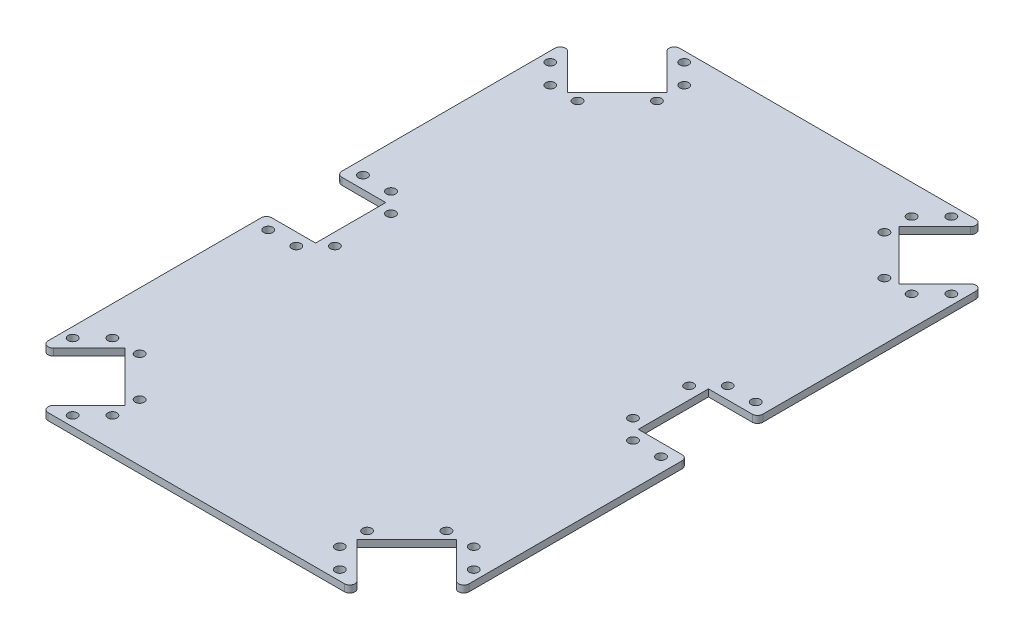
SolidWorks part; units mm, degrees
ref_plane "Front Plane" through (0, 0, 0) normal (0, 0, 1) x (1, 0, 0)
ref_plane "Top Plane" through (0, 0, 0) normal (0, 1, 0) x (1, 0, 0)
ref_plane "Right Plane" through (0, 0, 0) normal (1, 0, 0) x (0, 0, -1)
sketch "Sketch2" plane through (0, 0, 0) normal (0, 1, 0) x (1, 0, 0)
  line L0 (-60, 0) -> (60, 0) construction
  line L1 (-60, 90) -> (60, 90)
  line L2 (-60, 90) -> (-60, -90)
  line L3 (-60, -90) -> (60, -90)
  line L4 (60, 90) -> (60, -90)
  line L5 (60, 90) -> (0, 30) construction
  line L7 (0, 90) -> (0, -90) construction
  line L8 (32.4228, 73.7365) -> (28.5337, 77.6256) construction
  line L9 (28.5337, 77.6256) -> (32.4228, 81.5147) construction
  line L10 (32.4228, 81.5147) -> (38.0797, 87.1716) construction
  line L11 (38.0797, 87.1716) -> (40.9081, 90) construction
  circle A5 centre (32.4228, 73.7365) radius 1.3
  circle A6 centre (32.4228, 81.5147) radius 1.3
  circle A7 centre (38.0797, 87.1716) radius 1.3
  circle A8 centre (56, 13.5) radius 1.3
  circle A9 centre (48, 13.5) radius 1.3
  circle A10 centre (42.5, 8) radius 1.3
  circle A11 centre (42.5, -8) radius 1.3
  circle A12 centre (48, -13.5) radius 1.3
  circle A13 centre (56, -13.5) radius 1.3
  circle A14 centre (57.1716, 68.0797) radius 1.3
  circle A15 centre (51.5147, 62.4228) radius 1.3
  circle A16 centre (43.7365, 62.4228) radius 1.3
  circle A17 centre (57.1716, -68.0797) radius 1.3
  circle A18 centre (51.5147, -62.4228) radius 1.3
  circle A19 centre (43.7365, -62.4228) radius 1.3
  circle A20 centre (38.0797, -87.1716) radius 1.3
  circle A21 centre (32.4228, -81.5147) radius 1.3
  circle A22 centre (32.4228, -73.7365) radius 1.3
  circle A23 centre (-38.0797, 87.1716) radius 1.3
  circle A24 centre (-32.4228, 81.5147) radius 1.3
  circle A25 centre (-32.4228, 73.7365) radius 1.3
  circle A26 centre (-57.1716, 68.0797) radius 1.3
  circle A27 centre (-51.5147, 62.4228) radius 1.3
  circle A28 centre (-43.7365, 62.4228) radius 1.3
  circle A29 centre (-57.1716, -68.0797) radius 1.3
  circle A30 centre (-51.5147, -62.4228) radius 1.3
  circle A31 centre (-43.7365, -62.4228) radius 1.3
  circle A32 centre (-32.4228, -73.7365) radius 1.3
  circle A33 centre (-32.4228, -81.5147) radius 1.3
  circle A34 centre (-38.0797, -87.1716) radius 1.3
  circle A35 centre (-42.5, -8) radius 1.3
  circle A36 centre (-48, -13.5) radius 1.3
  circle A37 centre (-56, -13.5) radius 1.3
  circle A38 centre (-56, 13.5) radius 1.3
  circle A39 centre (-48, 13.5) radius 1.3
  circle A40 centre (-42.5, 8) radius 1.3
  point P0 (0, 0)
  point P24 (0, 0)
  point P26 (0, 0)
  point P27 (0, 0)
  point P40 (32.7378, 8)
  point P41 (0, 0)
  point P42 (0, 0)
  dimension "D6" = 5.5
  dimension "D10" = 8
  dimension "D11" = 5.5
  dimension "D2" = 2.6
  dimension "D3" = 8
  dimension "D4" = 4
  dimension "D5" = 5.5
  dimension "D7" = 45
  dimension "D8" = 120
  dimension "D9" = 180
  dimension "D12" = 5.5
  dimension "D13" = 8
  dimension "D14" = 4
  dimension "D15" = 8
extrude "Boss-Extrude1" add sketch "Sketch2" along normal blind 2
sketch "Sketch3" plane through (0, 2, 0) normal (0, 1, 0) x (1, 0, 0)
  line L0 (0, -90) -> (0, 90) construction
  line L1 (-60, -90) -> (60, -90) construction
  line L2 (60, 90) -> (-60, 90) construction
  line L3 (-60, 0) -> (60, 0) construction
  line L4 (-60, 90) -> (-60, -90) construction
  line L5 (60, -90) -> (60, 90) construction
  line L6 (60, 90) -> (0, 30) construction
  line L7 (60, -10) -> (46, -10)
  line L8 (60, -10) -> (60, 10)
  line L9 (60, 10) -> (46, 10)
  line L10 (46, -10) -> (46, 10)
  line L11 (45.8579, 90) -> (33.1299, 77.2721)
  line L12 (33.1299, 77.2721) -> (47.2721, 63.1299)
  line L13 (47.2721, 63.1299) -> (60, 75.8579)
  line L14 (60, 75.8579) -> (60, 90)
  line L15 (60, 90) -> (45.8579, 90)
  line L16 (60, -75.8579) -> (60, -90)
  line L17 (47.2721, -63.1299) -> (60, -75.8579)
  line L18 (33.1299, -77.2721) -> (47.2721, -63.1299)
  line L19 (45.8579, -90) -> (33.1299, -77.2721)
  line L20 (60, -90) -> (45.8579, -90)
  line L21 (-60, 75.8579) -> (-60, 90)
  line L22 (-47.2721, 63.1299) -> (-60, 75.8579)
  line L23 (-33.1299, 77.2721) -> (-47.2721, 63.1299)
  line L24 (-45.8579, 90) -> (-33.1299, 77.2721)
  line L25 (-60, 90) -> (-45.8579, 90)
  line L26 (-60, 10) -> (-46, 10)
  line L27 (-46, -10) -> (-46, 10)
  line L28 (-60, -10) -> (-46, -10)
  line L29 (-60, -10) -> (-60, 10)
  line L30 (-47.2721, -63.1299) -> (-60, -75.8579)
  line L31 (-33.1299, -77.2721) -> (-47.2721, -63.1299)
  line L32 (-45.8579, -90) -> (-33.1299, -77.2721)
  line L33 (-60, -90) -> (-45.8579, -90)
  line L34 (-60, -75.8579) -> (-60, -90)
  dimension "D1" = 10
  dimension "D2" = 20
  dimension "D3" = 14
  dimension "D4" = 45
  dimension "D5" = 18
  dimension "D6" = 20
  dimension "D7" = 10
extrude "Cut-Extrude1" cut sketch "Sketch3" against normal up to surface (2 mm away) up to face at (0, 0, 0)
fillet "Fillet1" radius 1.5 12 edges at (-60, 1, 10) (-60, 1, -10) (-60, 1, 75.8579) (-45.8579, 1, 90) (45.8579, 1, 90) (60, 1, 75.8579) (60, 1, 10) (60, 1, -10) (60, 1, -75.8579) (45.8579, 1, -90) (-60, 1, -75.8579) (-45.8579, 1, -90)
